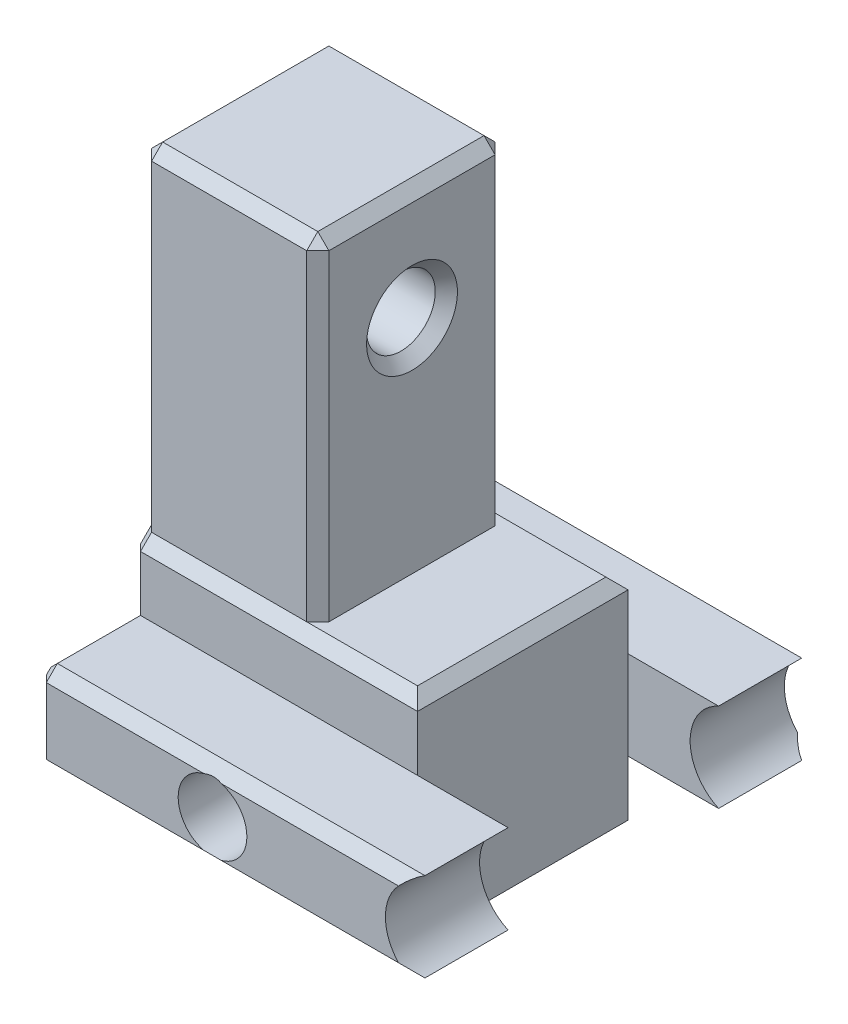
SolidWorks part; units mm, degrees
ref_plane "Front Plane" through (0, 0, 0) normal (0, 0, 1) x (1, 0, 0)
ref_plane "Top Plane" through (0, 0, 0) normal (0, 1, 0) x (1, 0, 0)
ref_plane "Right Plane" through (0, 0, 0) normal (1, 0, 0) x (0, 0, -1)
sketch "Sketch1" plane through (0, 0, 0) normal (0, 0, 1) x (1, 0, 0)
  line L0 (-0.9165, 2) -> (-50, 2)
  line L1 (-50, 2) -> (-50, -2)
  line L3 (-50, -2) -> (-0.9165, -2)
  arc A0 (-0.9165, 2) -> (-0.9165, -2) centre (0, 0) ccw
  dimension "D2" = 4
  dimension "D1" = 2.2
  dimension "D3" = 2
  dimension "D4" = 50
extrude "Boss-Extrude1" add sketch "Sketch1" along normal blind 18
sketch "Sketch2" plane through (-50, 0, 0) normal (-1, 0, 0) x (0, 0, 1)
  line L1 (4.25, 5) -> (13.75, 5)
  line L2 (4.25, 5) -> (4.25, -5)
  line L3 (4.25, -5) -> (13.75, -5)
  line L4 (13.75, 5) -> (13.75, -5)
  line L6 (18, 2) -> (18, -2) construction
  line L7 (18, 2) -> (0, 2) construction
  point P4 (4.25, 0)
  point P7 (18, 0)
  point P8 (9, 5)
  point P11 (9, 2)
  dimension "D1" = 9.5
  dimension "D3" = 10
extrude "Boss-Extrude2" add sketch "Sketch2" against normal up to vertex (49.0835 mm away) up to point (-0.9165, 2, 18)
sketch "Sketch3" plane through (0, 2, 0) normal (0, 1, 0) x (1, 0, 0)
  line L1 (-0.9165, -4.25) -> (4.0835, -4.25)
  line L2 (-0.9165, -4.25) -> (-0.9165, -13.75)
  line L3 (-0.9165, -13.75) -> (4.0835, -13.75)
  line L4 (4.0835, -4.25) -> (4.0835, -13.75)
  dimension "D1" = 9.5
  dimension "D2" = 5
sketch "Sketch4" plane through (0, 0, 18) normal (0, 0, 1) x (1, 0, 0)
  line L0 (-0.9165, 2) -> (-50, 2) construction
  point P0 (-10, 0)
  dimension "D1" = 10
  dimension "D2" = 2
hole_wizard "M3 Clearance Hole1" positions "Sketch5" profile "Sketch6" hole size "M3" standard "DIN" end condition through all
sketch "Sketch5" plane through (0, 0, 18) normal (0, 0, 1) x (1, 0, 0)
  point P0 (-10, 0)
sketch "Sketch6" plane through (-10, 0, 18) normal (1, 0, 0) x (0, -1, 0)
  line L0 (0, 0) -> (0, 18)
  line L1 (0, 18) -> (1.55, 18)
  line L2 (1.55, 18) -> (1.55, 0)
  line L5 (1.55, 0) -> (0, 0)
  line L11 (0, -6.35) -> (0, 107.95) construction
  dimension "Thru Hole Dia." = 3.1
  dimension "Thru Hole Depth" = 18
sketch "Sketch7" plane through (-50, 0, 0) normal (-1, 0, 0) x (0, 0, 1)
  line L0 (0, 2) -> (0, -2)
  line L1 (0, -2) -> (4.25, -2)
  line L2 (4.25, -2) -> (4.25, -5)
  line L3 (4.25, -5) -> (13.75, -5)
  line L4 (13.75, -5) -> (13.75, -2)
  line L5 (13.75, -2) -> (18, -2)
  line L6 (18, -2) -> (18, 2)
  line L7 (18, 2) -> (13.75, 2)
  line L8 (13.75, 2) -> (13.75, 5)
  line L9 (13.75, 5) -> (4.25, 5)
  line L10 (4.25, 5) -> (4.25, 2)
  line L11 (4.25, 2) -> (0, 2)
extrude "Boss-Extrude3" add sketch "Sketch7" along normal blind 1.5
chamfer "Chamfer1" distance 0.5 angle 45 8 edges at (-26.2083, -5, 4.25) (-26.2083, -5, 13.75) (-26.2083, 5, 13.75) (-26.2083, 5, 4.25) (-26.2083, -2, 0) (-26.2083, 2, 0) (-26.2083, -2, 18) (-26.2083, 2, 18)
sketch "Sketch8" plane through (0, 5, 0) normal (0, 1, 0) x (1, 0, 0)
  line L0 (-51.5, -4.25) -> (-0.9165, -4.25) construction
  line L1 (0, -4.25) -> (-5, -4.25)
  line L2 (0, -4.25) -> (0, -13.75)
  line L3 (0, -13.75) -> (-5, -13.75)
  line L4 (-5, -4.25) -> (-5, -13.75)
  line L5 (-0.9165, -13.75) -> (-51.5, -13.75) construction
  dimension "D1" = 5
extrude "Cut-Extrude1" cut sketch "Sketch8" against normal through all
sketch "Sketch9" plane through (0, 5, 0) normal (0, 1, 0) x (1, 0, 0)
  line L0 (-5, -4.75) -> (-51.5, -4.75) construction
  line L1 (-10, -4.75) -> (-18, -4.75)
  line L2 (-10, -4.75) -> (-10, -13.25)
  line L3 (-10, -13.25) -> (-18, -13.25)
  line L4 (-18, -4.75) -> (-18, -13.25)
  line L5 (-51.5, -13.25) -> (-5, -13.25) construction
  line L6 (-5, -4.75) -> (-5, -13.25) construction
  line L8 (0, 0) -> (0, -18.6346) construction
  dimension "D1" = 5
  dimension "D2" = 18
extrude "Boss-Extrude4" add sketch "Sketch9" along normal blind 15
sketch "Sketch10" plane through (-10, 0, 0) normal (-1, 0, 0) x (0, 0, 1)
  line L1 (4.75, 5) -> (13.25, 5) construction
  line L2 (4.75, 20) -> (13.25, 20) construction
  circle A0 centre (9, 15) radius 1.55
  point P7 (9, 20)
  dimension "D1" = 3.1
  dimension "D2" = 10
sketch "Sketch13" plane through (0, 20, 0) normal (0, 1, 0) x (1, 0, 0)
  line L0 (-18, -4.75) -> (-18, -13.25) construction
  line L1 (-51.5, 0) -> (-18, 0)
  line L2 (-51.5, 0) -> (-51.5, -18)
  line L3 (-51.5, -18) -> (-18, -18)
  line L4 (-18, 0) -> (-18, -18)
  line L5 (-10.3905, -18) -> (-51.5, -18) construction
  line L6 (-51.5, 0) -> (-10.3905, 0) construction
  line L7 (-51.5, -13.25) -> (-51.5, -4.75) construction
extrude "Cut-Extrude5" cut sketch "Sketch13" against normal through all
extrude "Cut-Extrude6" cut sketch "Sketch10" along normal blind 2.6
chamfer "Chamfer2" distance 0.5 angle 45 30 edges at (-5, -5, 9) (-5, 5, 9) (-14, 20, 13.25) (-18, 20, 9) (-18, 12.5, 13.25) (-18, 4.75, 13.5) (-18, 3.25, 13.75) (-18, 2, 15.625) (-18, 1.75, 17.75) (-18, 0, 18) (-18, -1.75, 17.75) (-18, -2, 15.625) (-18, -3.25, 13.75) (-18, -4.75, 13.5) (-18, -5, 9) (-18, -4.75, 4.5) (-18, -3.25, 4.25) (-18, -2, 2.375) (-18, -1.75, 0.25) (-18, 0, 0) (-18, 1.75, 0.25) (-18, 2, 2.375) (-18, 3.25, 4.25) (-18, 4.75, 4.5) (-18, 12.5, 4.75) (-14, 20, 4.75) (-10, 12.5, 13.25) (-10, 20, 9) (-10, 12.5, 4.75) (-10, 15, 10.55)
